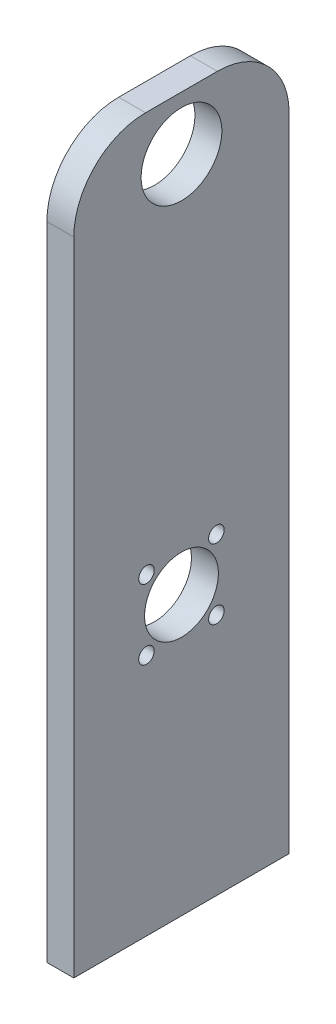
SolidWorks part; units mm, degrees
ref_plane "Front Plane" through (0, 0, 0) normal (0, 0, 1) x (1, 0, 0)
ref_plane "Top Plane" through (0, 0, 0) normal (0, 1, 0) x (1, 0, 0)
ref_plane "Right Plane" through (0, 0, 0) normal (1, 0, 0) x (0, 0, -1)
sketch "Sketch1" plane through (0, 0, 0) normal (0, 1, 0) x (1, 0, 0)
  line L1 (-4.7625, 38.1) -> (4.7625, 38.1)
  line L2 (-4.7625, 38.1) -> (-4.7625, -38.1)
  line L3 (-4.7625, -38.1) -> (4.7625, -38.1)
  line L4 (4.7625, 38.1) -> (4.7625, -38.1)
  line L5 (-4.7625, 38.1) -> (4.7625, -38.1) construction
  line L6 (-4.7625, -38.1) -> (4.7625, 38.1) construction
  point P0 (0, 0)
  dimension "D1" = 76.2
  dimension "D2" = 9.525
extrude "Boss-Extrude1" add sketch "Sketch1" along normal mid plane 252.476
sketch "Sketch3" plane through (-4.7625, 0, 0) normal (-1, 0, 0) x (0, 0, 1)
  line L0 (-45.1772, -15.4437) -> (44.4211, -15.4437) construction
  line L1 (-45.1772, -40.1878) -> (44.4211, -40.1878) construction
  line L2 (-38.1, 126.238) -> (38.1, 126.238) construction
  line L3 (-45.1772, -27.813) -> (44.4211, -27.813) construction
  line L4 (-12.3658, -8.7664) -> (-12.3658, -58.1325) construction
  line L5 (12.3748, -8.7664) -> (12.3748, -58.1325) construction
  line L6 (0, -8.7664) -> (0, -58.1325) construction
  circle A0 centre (0, 107.188) radius 14.2875
  circle A1 centre (-12.3658, -15.4437) radius 2.75
  circle A2 centre (12.3748, -15.4437) radius 2.75
  circle A3 centre (-12.3658, -40.1878) radius 2.75
  circle A4 centre (12.3748, -40.1878) radius 2.75
  circle A5 centre (0, -27.813) radius 13.0556
  point P12 (-38.1, 126.238)
  dimension "D1" = 28.575
  dimension "D2" = 19.05
  dimension "D3" = 12.3658
  dimension "D4" = 12.3748
  dimension "D7" = 26.1112
  dimension "D8" = 5.5
  dimension "D5" = 12.3693
  dimension "D6" = 12.3748
  dimension "D9" = 24.7406
extrude "Cut-Extrude2" cut sketch "Sketch3" against normal blind 45.974
fillet "Fillet1" radius 25.4 2 edges at (0, 126.238, 38.1) (0, 126.238, -38.1)
sketch "Sketch4" plane through (-4.7625, 0, 0) normal (-1, 0, 0) x (0, 0, 1)
  line L0 (-38.1, 100.838) -> (-38.1, -126.238) construction
  circle A0 centre (-1.5, 11.3124) radius 2.5
  circle A1 centre (-1.5, -54.6876) radius 2.5
  circle A2 centre (0, -21.6876) radius 7.9248
  dimension "D4" = 36.6
  dimension "D5" = 5
  dimension "D2" = 15.8496
  dimension "D1" = 66
  dimension "D3" = 33
  dimension "D6" = 1.5
  dimension "D7" = 1.5
  dimension "D8" = 38.1
extrude "Cut-Extrude3" [suppressed] cut sketch "Sketch4" against normal through all
